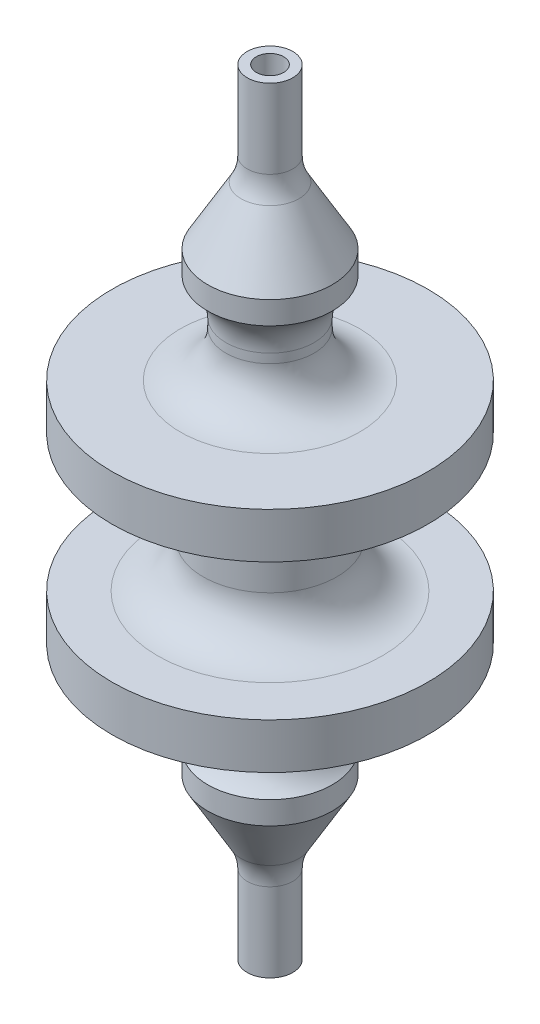
SolidWorks part; units mm, degrees
ref_plane "Alzado" through (0, 0, 0) normal (0, 0, 1) x (1, 0, 0)
ref_plane "Planta" through (0, 0, 0) normal (0, 1, 0) x (1, 0, 0)
ref_plane "Vista lateral" through (0, 0, 0) normal (1, 0, 0) x (0, 0, -1)
sketch "Croquis1" plane through (0, 0, 0) normal (0, 0, 1) x (1, 0, 0)
  line L0 (0.082, -29.4659) -> (0.082, 270.5341) construction
  line L1 (0.082, 1.3319) -> (-0.418, 1.3319)
  line L2 (-0.418, 1.3319) -> (-0.418, -0.6681)
  line L3 (-0.418, -0.6681) -> (-1.284, -2.1681)
  line L4 (-1.284, -2.1681) -> (-1.284, -2.6681)
  line L5 (-1.284, -2.6681) -> (-0.884, -2.6681)
  line L6 (-0.884, -2.6681) -> (-0.884, -4.6681)
  line L7 (-0.884, -4.6681) -> (-3.384, -4.6681)
  line L8 (-3.384, -4.6681) -> (-3.384, -5.6681)
  line L9 (-3.384, -5.6681) -> (-1.384, -5.6681)
  line L10 (-1.384, -5.6681) -> (-1.384, -8.6681)
  line L11 (-1.384, -7.1681) -> (9.8743, -7.1681) construction
  line L12 (-3.384, -8.6681) -> (-1.384, -8.6681)
  line L13 (-3.384, -9.6681) -> (-3.384, -8.6681)
  line L14 (-0.884, -9.6681) -> (-3.384, -9.6681)
  line L15 (-0.884, -11.6681) -> (-0.884, -9.6681)
  line L16 (-1.284, -11.6681) -> (-0.884, -11.6681)
  line L17 (-1.284, -12.1681) -> (-1.284, -11.6681)
  line L18 (-0.418, -13.6681) -> (-1.284, -12.1681)
  line L19 (-0.418, -15.6681) -> (-0.418, -13.6681)
  line L20 (0.082, -15.6681) -> (-0.418, -15.6681)
  line L21 (0.082, 1.3319) -> (0.082, -15.6681)
  dimension "D1" = 0.5
  dimension "D2" = 2
  dimension "D3" = 300
  dimension "D4" = 30
  dimension "D5" = 1.5
  dimension "D6" = 0.5
  dimension "D7" = 2
  dimension "D8" = 2.5
  dimension "D9" = 1
  dimension "D10" = 2
  dimension "D11" = 1.5
  dimension "D12" = 0.4
revolve "Revolución1" add sketch "Croquis1" angle 360 about L0
fillet "Redondeo1" radius 1 8 edges at (0.082, -13.6681, -0.5) (0.082, -0.6681, -0.5) (0.082, -9.6681, -0.966) (0.082, -8.6681, -1.466) (0.082, -5.6681, -1.466) (0.082, -4.6681, -0.966) (0.082, -2.6681, -0.966) (0.082, -11.6681, -0.966)
sketch "Croquis2" plane through (0, 1.3319, 0) normal (0, 1, 0) x (1, 0, 0)
  circle A1 centre (0.082, 0) radius 0.3
  circle A2 centre (0.082, 0) radius 0.5
  circle A3 centre (0.082, 0) radius 0.5
  dimension "D1" = 0
extrude "Cortar-Extruir1" cut sketch "Croquis2" against normal blind 30 contours A1
